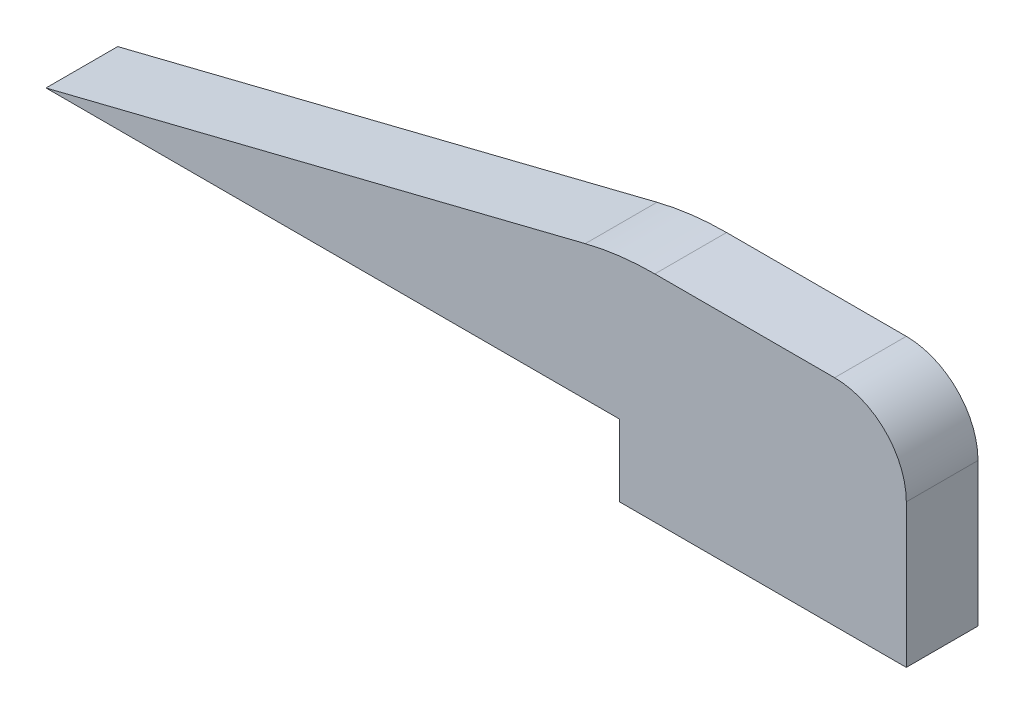
SolidWorks part; units mm, degrees
ref_plane "Front Plane" through (0, 0, 0) normal (0, 0, 1) x (1, 0, 0)
ref_plane "Top Plane" through (0, 0, 0) normal (0, 1, 0) x (1, 0, 0)
ref_plane "Right Plane" through (0, 0, 0) normal (1, 0, 0) x (0, 0, -1)
sketch "Sketch1" plane through (0, 0, 0) normal (0, 0, 1) x (1, 0, 0)
  line L0 (0, 0) -> (23.8832, 5.9708)
  line L1 (26.9634, 6.35) -> (34.925, 6.35)
  line L4 (38.1, -3.175) -> (25.4, -3.175)
  line L5 (25.4, -3.175) -> (25.4, 0)
  line L6 (25.4, 0) -> (0, 0)
  line L7 (38.1, 3.175) -> (38.1, -3.175)
  arc A0 (23.8832, 5.9708) -> (26.9634, 6.35) centre (26.9634, -6.35) cw
  arc A2 (34.925, 6.35) -> (38.1, 3.175) centre (34.925, 3.175) cw
  point P11 (25.4, 6.35)
  dimension "D1" = 12.7
  dimension "D2" = 3.175
  dimension "D6" = 3.175
  dimension "D3" = 25.4
  dimension "D4" = 6.35
  dimension "D5" = 12.7
extrude "Boss-Extrude1" add sketch "Sketch1" along normal blind 3.175
